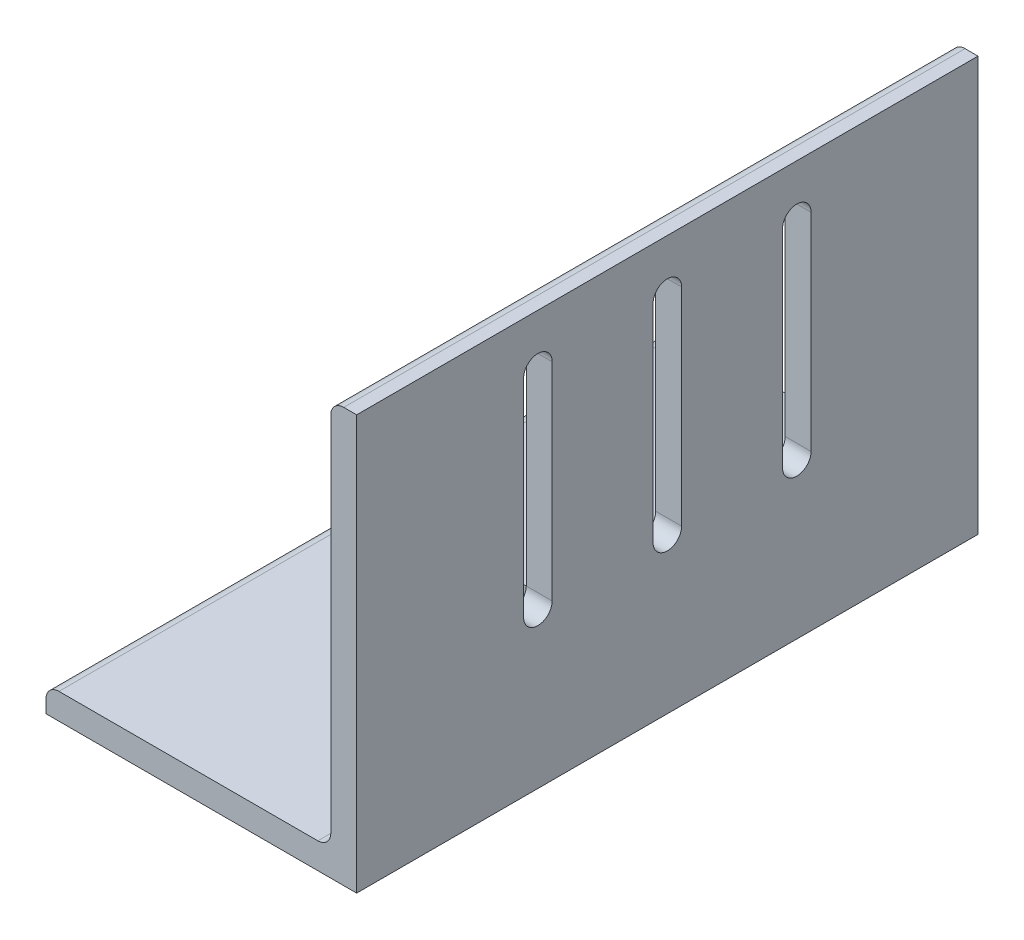
SolidWorks part; units mm, degrees
ref_plane "Front Plane" through (0, 0, 0) normal (0, 0, 1) x (1, 0, 0)
ref_plane "Top Plane" through (0, 0, 0) normal (0, 1, 0) x (1, 0, 0)
ref_plane "Right Plane" through (0, 0, 0) normal (1, 0, 0) x (0, 0, -1)
sketch "Sketch2" plane through (0, 0, 0) normal (0, 0, 1) x (1, 0, 0)
  line L0 (-38.1, 0) -> (38.1, 0)
  line L1 (38.1, 0) -> (38.1, 101.6)
  line L2 (38.1, 101.6) -> (31.75, 101.6) construction
  line L3 (31.75, 98.425) -> (31.75, 9.525)
  line L4 (28.575, 6.35) -> (-34.925, 6.35)
  line L5 (-38.1, 0) -> (-38.1, 6.35) construction
  line L6 (34.925, 101.6) -> (38.1, 101.6)
  line L7 (-38.1, 3.175) -> (-38.1, 0)
  arc A0 (31.75, 98.425) -> (34.925, 101.6) centre (34.925, 98.425) cw
  arc A1 (-38.1, 3.175) -> (-34.925, 6.35) centre (-34.925, 3.175) cw
  arc A2 (31.75, 9.525) -> (28.575, 6.35) centre (28.575, 9.525) cw
  dimension "Vert" = 101.6
  dimension "Horz" = 76.2
  dimension "Thickness" = 6.35
extrude "Boss-Extrude1" add sketch "Sketch2" along normal mid plane 152.4
ref_plane "Contact Plane 1" through (0, 6.35, 0) normal (0, 1, 0) x (1, 0, 0)
ref_plane "Contact Plane 2" through (31.75, 0, 0) normal (-1, 0, 0) x (0, 0, 1)
sketch "Sketch3" plane through (38.1, 0, 0) normal (1, 0, 0) x (0, 0, -1)
  line L0 (-31.75, 88.9) -> (-31.75, 38.1) construction
  line L1 (-28.25, 88.9) -> (-28.25, 38.1)
  line L2 (-35.25, 88.9) -> (-35.25, 38.1)
  line L3 (0, 0) -> (0, 101.6) construction
  line L4 (-76.2, 0) -> (76.2, 0) construction
  line L5 (-76.2, 101.6) -> (76.2, 101.6) construction
  line L6 (31.75, 88.9) -> (31.75, 38.1) construction
  line L7 (28.25, 88.9) -> (28.25, 38.1)
  line L8 (35.25, 88.9) -> (35.25, 38.1)
  line L9 (0, 88.9) -> (0, 38.1) construction
  line L10 (3.5, 88.9) -> (3.5, 38.1)
  line L11 (-3.5, 88.9) -> (-3.5, 38.1)
  arc A0 (-28.25, 88.9) -> (-35.25, 88.9) centre (-31.75, 88.9) ccw
  arc A1 (-35.25, 38.1) -> (-28.25, 38.1) centre (-31.75, 38.1) ccw
  arc A2 (28.25, 88.9) -> (35.25, 88.9) centre (31.75, 88.9) cw
  arc A3 (35.25, 38.1) -> (28.25, 38.1) centre (31.75, 38.1) cw
  arc A4 (3.5, 88.9) -> (-3.5, 88.9) centre (0, 88.9) ccw
  arc A5 (-3.5, 38.1) -> (3.5, 38.1) centre (0, 38.1) ccw
  point P2 (-31.75, 63.5)
  point P15 (31.75, 63.5)
  point P22 (0, 63.5)
  dimension "D1" = 3.5
  dimension "D3" = 31.75
  dimension "D5" = 3.5
  dimension "D2" = 50.8
  dimension "D4" = 63.5
  dimension "D6" = 50.8
  dimension "D7" = 63.5
extrude "Cut-Extrude1" cut sketch "Sketch3" against normal blind 10
sketch "Sketch4" plane through (0, 0, 0) normal (0, -1, 0) x (1, 0, 0)
  line L0 (-38.1, 76.2) -> (-38.1, -76.2) construction
  line L1 (-38.1, -76.2) -> (38.1, -76.2) construction
  circle A0 centre (0, 25.4) radius 3.5
  circle A1 centre (0, -25.4) radius 3.5
  circle A2 centre (0, 0) radius 3.5
  dimension "D1" = 7
  dimension "D2" = 7
  dimension "D3" = 38.1
  dimension "D4" = 76.2
extrude "Cut-Extrude2" cut sketch "Sketch4" against normal blind 10
